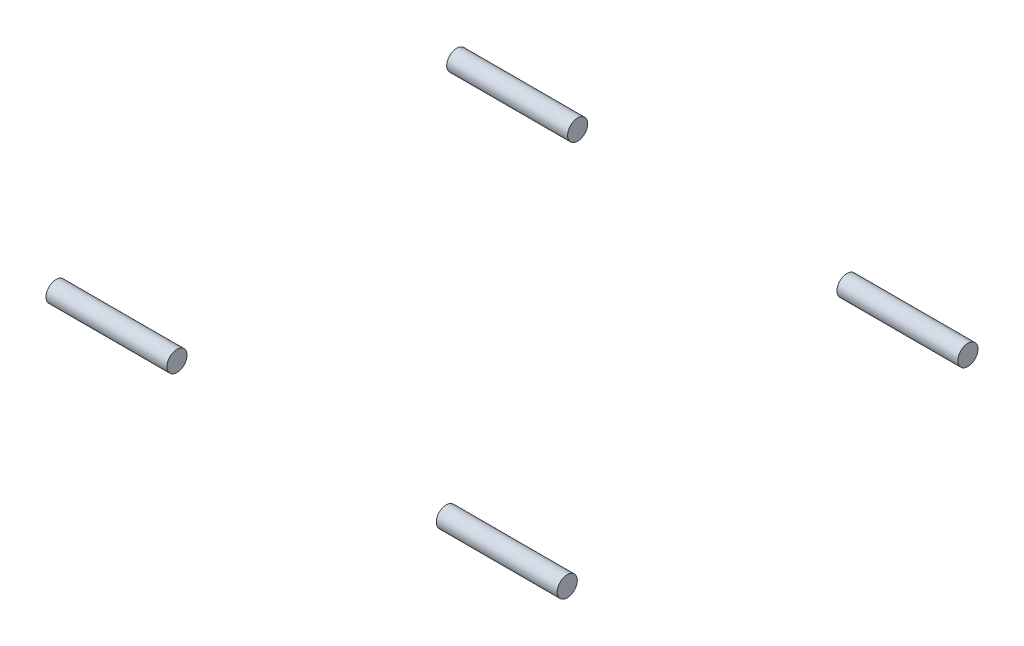
SolidWorks part; units mm, degrees
material "6061-T6 (SS)"
ref_plane "Front Plane" through (0, 0, 0) normal (0, 0, 1) x (1, 0, 0)
ref_plane "Top Plane" through (0, 0, 0) normal (0, 1, 0) x (1, 0, 0)
ref_plane "Right Plane" through (0, 0, 0) normal (1, 0, 0) x (0, 0, -1)
sketch "Sketch1" plane through (80.53, 0, 0) normal (-1, 0, 0) x (0, 0, 1)
  circle A0 centre (126.25, 0) radius 3.175
  circle A1 centre (0, 0) radius 3.175
  circle A2 centre (0, 0) radius 3.175 construction
  circle A3 centre (126.25, 0) radius 3.175 construction
extrude "Boss-Extrude1" add sketch "Sketch1" along normal blind 38.1
mirror "Mirror1" about plane through (0, 0, 0) normal (1, 0, 0) of bodies 101 102
